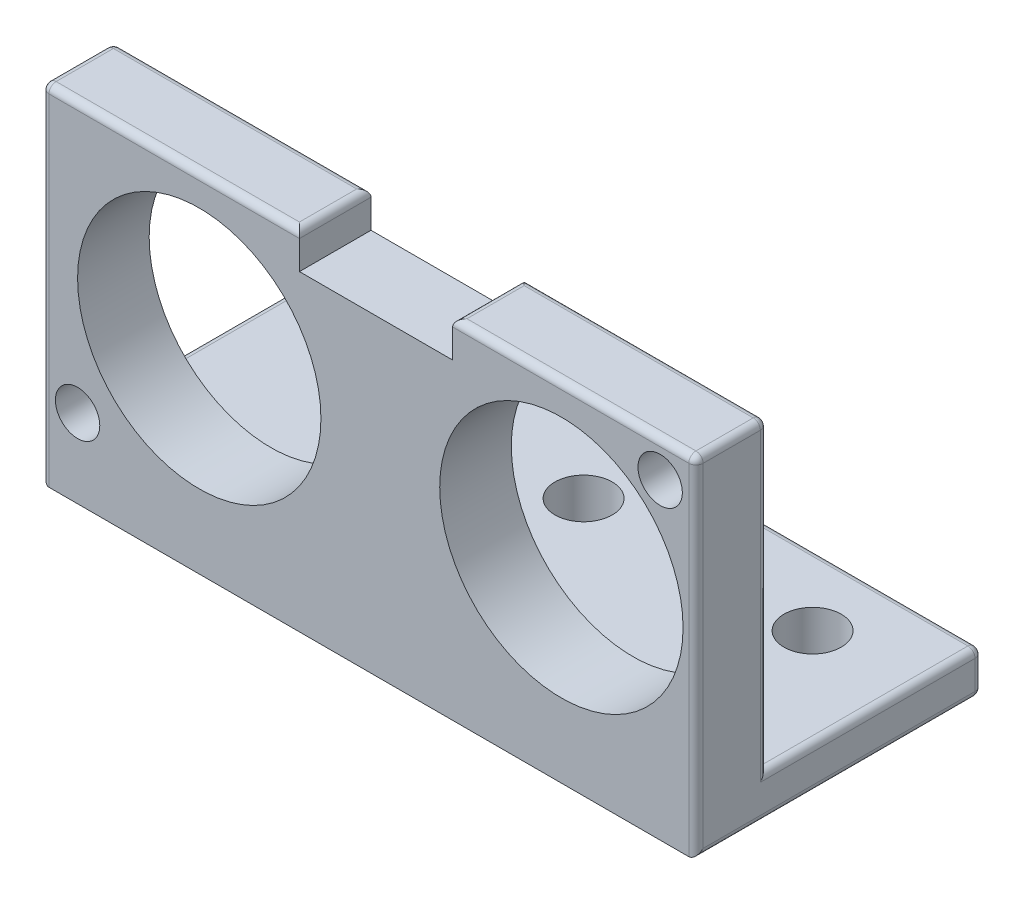
SolidWorks part; units mm, degrees
ref_plane "前基準面" through (0, 0, 0) normal (0, 0, 1) x (1, 0, 0)
ref_plane "上基準面" through (0, 0, 0) normal (0, 1, 0) x (1, 0, 0)
ref_plane "右基準面" through (0, 0, 0) normal (1, 0, 0) x (0, 0, -1)
sketch "草圖1" plane through (0, 0, 0) normal (0, 0, 1) x (1, 0, 0)
  line L1 (-22.85, 10.65) -> (22.85, 10.65)
  line L2 (-22.85, 10.65) -> (-22.85, -10.65)
  line L3 (-22.85, -10.65) -> (22.85, -10.65)
  line L4 (22.85, 10.65) -> (22.85, -10.65)
  line L5 (-22.85, 10.65) -> (22.85, -10.65) construction
  line L6 (-22.85, -10.65) -> (22.85, 10.65) construction
  point P0 (0, 0)
  dimension "D1" = 21.3
  dimension "D2" = 45.7
extrude "填料-伸長1" add sketch "草圖1" along normal blind 5
sketch "草圖2" plane through (0, 0, 5) normal (0, 0, 1) x (1, 0, 0)
  line L0 (-22.85, 10.65) -> (-22.85, -10.65) construction
  line L1 (-22.85, -10.65) -> (22.85, -10.65) construction
  line L2 (22.85, -10.65) -> (22.85, 10.65) construction
  line L3 (22.85, 10.65) -> (-22.85, 10.65) construction
  circle A0 centre (-20.35, -8.15) radius 1.55
  circle A1 centre (20.35, 8.15) radius 1.55
  circle A2 centre (-11.85, 0) radius 8.5
  circle A3 centre (13.45, 0) radius 8.5
  dimension "D1" = 3.1
  dimension "D4" = 3.1
  dimension "D6" = 2.5
  dimension "D7" = 17
  dimension "D8" = 17
  dimension "D2" = 2.5
  dimension "D3" = 2.5
  dimension "D5" = 2.5
  dimension "D9" = 11
  dimension "D10" = 9.4
extrude "除料-伸長1" cut sketch "草圖2" against normal blind 13.95 contours A1 | A3 | A0 | A2
sketch "草圖7" plane through (0, -10.65, 0) normal (0, -1, 0) x (1, 0, 0)
  line L0 (-22.85, 5) -> (-22.85, -15)
  line L1 (-22.85, -15) -> (22.85, -15)
  line L2 (22.85, -15) -> (22.85, 5)
  line L3 (22.85, 5) -> (-22.85, 5)
  line L4 (-22.85, 5) -> (22.85, 5) construction
  line L6 (22.85, 5) -> (22.85, 0) construction
  line L7 (-22.85, 5) -> (-22.85, 0) construction
  dimension "D1" = 20
extrude "填料-伸長3" add sketch "草圖7" along normal blind 3
sketch "草圖3" plane through (0, 0, 5) normal (0, 0, 1) x (1, 0, 0)
  line L1 (-4.85, 10.65) -> (5.85, 10.65)
  line L2 (-4.85, 10.65) -> (-4.85, 8.15)
  line L3 (-4.85, 8.15) -> (5.85, 8.15)
  line L4 (5.85, 10.65) -> (5.85, 8.15)
  line L5 (-4.85, 10.65) -> (5.85, 8.15) construction
  line L6 (-4.85, 8.15) -> (5.85, 10.65) construction
  line L8 (-22.85, 10.65) -> (-22.85, -13.65) construction
  line L10 (22.85, -13.65) -> (22.85, 10.65) construction
  line L11 (22.85, 10.65) -> (-22.85, 10.65) construction
  point P0 (0.5, 9.4)
  dimension "D1" = 18
  dimension "D2" = 17
  dimension "D3" = 2.5
extrude "除料-伸長2" cut sketch "草圖3" against normal blind 13.95
fillet "圓角4" radius 0.5 18 edges at (14.35, 10.65, 5) (5.85, 10.65, 2.5) (14.35, 10.65, 0) (-13.85, 10.65, 0) (-4.85, 10.65, 2.5) (-13.85, 10.65, 5) (-22.85, 10.65, 2.5) (-22.85, -1.5, 5) (-22.85, -13.65, -5) (-22.85, -12.15, -15) (22.85, -12.15, -15) (22.85, -13.65, -5) (22.85, -1.5, 5) (22.85, 10.65, 2.5)
sketch "草圖8" plane through (0, -10.65, 0) normal (0, 1, 0) x (1, 0, 0)
  line L0 (22.85, 14.5) -> (22.85, -0.5) construction
  line L2 (-22.35, 15) -> (22.35, 15) construction
  circle A0 centre (18.85, 10) radius 2
  dimension "D1" = 4
  dimension "D2" = 4
  dimension "D3" = 5
sketch "草圖9" plane through (0, -10.65, 0) normal (0, 1, 0) x (1, 0, 0)
  line L0 (0, 13.073) -> (0, -11.293) construction
  line L1 (28.6432, 0) -> (-30.902, 0) construction
sketch "草圖11" plane through (0, -10.65, 0) normal (0, 1, 0) x (1, 0, 0)
  line L0 (-4.85, -5) -> (-22.35, -5) construction
  circle A0 centre (0, 10) radius 2
  circle A1 centre (16, 10) radius 2
  circle A2 centre (-16, 10) radius 2
  dimension "D3" = 4
  dimension "D1" = 15
  dimension "D2" = 2
  dimension "D4" = 2
extrude "除料-伸長4" cut sketch "草圖11" against normal blind 3
fillet "圓角5" radius 0.5 6 edges at (-22.7036, -10.7964, -14.8536) (22.7036, -10.7964, -14.8536) (-22.7036, -13.5036, -14.8536) (22.7036, -13.5036, -14.8536) (0, -10.65, -15) (0, -13.65, -15)
